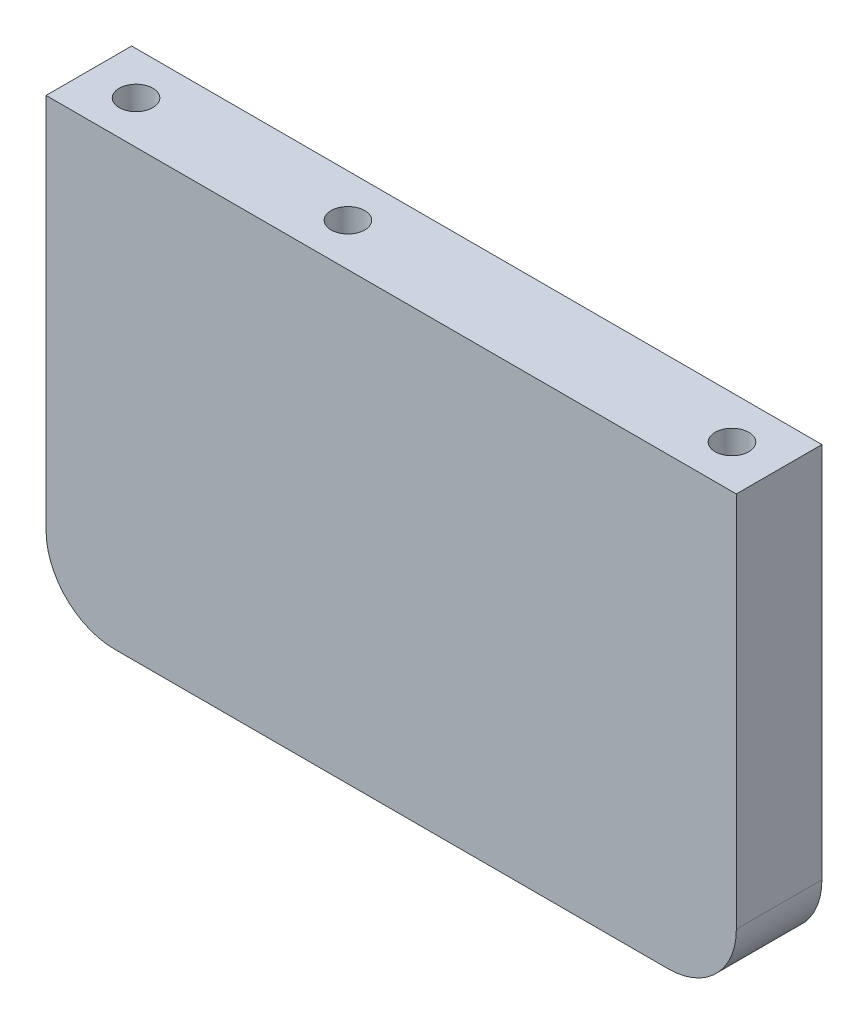
SolidWorks part; units mm, degrees
ref_plane "Front Plane" through (0, 0, 0) normal (0, 0, 1) x (1, 0, 0)
ref_plane "Top Plane" through (0, 0, 0) normal (0, 1, 0) x (1, 0, 0)
ref_plane "Right Plane" through (0, 0, 0) normal (1, 0, 0) x (0, 0, -1)
sketch "Sketch1" plane through (0, 0, 0) normal (0, 0, 1) x (1, 0, 0)
  line L10 (-33.225, 19.05) -> (18, 19.05)
  line L11 (-33.225, 19.05) -> (-33.225, -14)
  line L12 (-33.225, -14) -> (18, -14)
  line L13 (18, 19.05) -> (18, -14)
  circle A2 centre (0, 0) radius 11.1 construction
  circle A3 centre (-22.225, 0) radius 3.556 construction
  dimension "D2" = 7.112
  dimension "D5" = 19.05
  dimension "D6" = 11
  dimension "D3" = 22.225
  dimension "D1" = 22.2
  dimension "D8" = 51.225
  dimension "D4" = 14
  dimension "D7" = 18
extrude "Boss-Extrude1" add sketch "Sketch1" against normal blind 6.35
sketch "Sketch8" plane through (0, 19.05, 0) normal (0, 1, 0) x (1, 0, 0)
  line L0 (-33.225, 3.175) -> (18, 3.175) construction
  line L1 (-33.225, 6.35) -> (-33.225, 0) construction
  line L2 (18, 6.35) -> (18, 0) construction
  circle A1 centre (-29.725, 3.175) radius 1.25
  circle A2 centre (-14, 3.175) radius 1.25
  circle A3 centre (14.5, 3.175) radius 1.25
  dimension "D1" = 2.5
  dimension "D2" = 3.5
  dimension "D3" = 3.5
  dimension "D4" = 14
extrude "Cut-Extrude4" cut sketch "Sketch8" against normal blind 15
fillet "Fillet3" radius 5.08 2 edges at (18, -14, -3.175) (-33.225, -14, -3.175)
sketch "Sketch10" plane through (0, 0, -6.35) normal (0, 0, -1) x (-1, 0, 0)
  circle A0 centre (22.225, 0) radius 3.556 construction
  circle A1 centre (0, 0) radius 11.1 construction
  circle A2 centre (22.225, 0) radius 3.556
  circle A3 centre (0, 0) radius 11.1
extrude "Cut-Extrude5" cut sketch "Sketch10" against normal offset from surface (4.7625 mm away) 1.5875 up to face at (-7.6125, -1.6407, 0)
